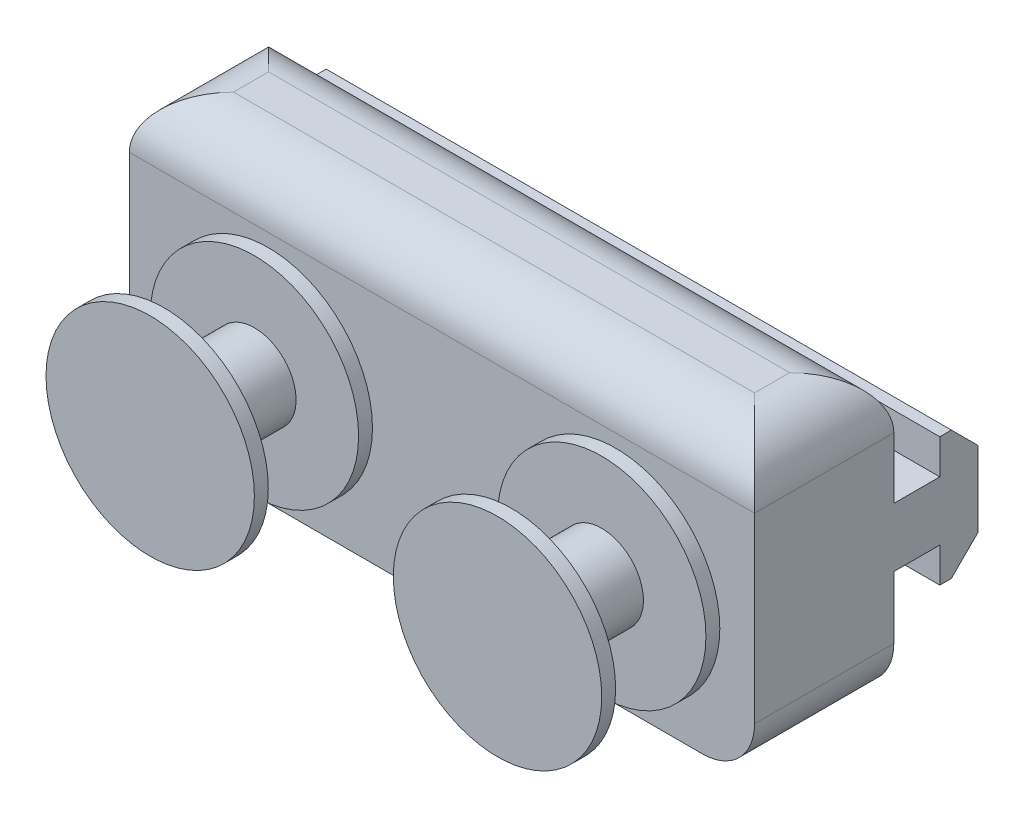
SolidWorks part; units mm, degrees
ref_plane "Front Plane" through (0, 0, 0) normal (0, 0, 1) x (1, 0, 0)
ref_plane "Top Plane" through (0, 0, 0) normal (0, 1, 0) x (1, 0, 0)
ref_plane "Right Plane" through (0, 0, 0) normal (1, 0, 0) x (0, 0, -1)
sketch "Sketch2" plane through (0, 0, 0) normal (1, 0, 0) x (0, 0, -1)
  line L0 (20, -17) -> (20, -5) construction
  line L1 (20, -5) -> (14.5, -5) construction
  line L2 (14.5, -5) -> (14.5, -10) construction
  line L3 (14.5, -10) -> (11.7678, -10) construction
  line L4 (11.7678, -10) -> (7.5, -5.7322) construction
  line L5 (7.5, -5.7322) -> (7.5, -0.5196) construction
  line L6 (7.5, -0.5196) -> (7.2, 0) construction
  line L7 (7.2, 0) -> (7.5, 0.5196) construction
  line L8 (7.5, 0.5196) -> (7.5, 5.7322) construction
  line L9 (7.5, 5.7322) -> (11.7678, 10) construction
  line L10 (11.7678, 10) -> (14.5, 10) construction
  line L11 (14.5, 10) -> (14.5, 5) construction
  line L12 (14.5, 5) -> (20, 5) construction
  line L13 (20, 5) -> (20, 16.9163) construction
  line L14 (17, 19.9163) -> (5, 19.9163) construction
  line L15 (5, 19.9163) -> (5, 14.5) construction
  line L16 (5, 14.5) -> (10, 14.5) construction
  line L17 (10, 14.5) -> (10, 11.7678) construction
  line L18 (10, 11.7678) -> (5.7322, 7.5) construction
  line L19 (5.7322, 7.5) -> (0.5196, 7.5) construction
  line L20 (0.5196, 7.5) -> (0, 7.2) construction
  line L21 (0, 7.2) -> (-0.5196, 7.5) construction
  line L22 (-0.5196, 7.5) -> (-5.7322, 7.5) construction
  line L23 (-5.7322, 7.5) -> (-10, 11.7678) construction
  line L24 (-10, 11.7678) -> (-10, 14.5) construction
  line L25 (-10, 14.5) -> (-5, 14.5) construction
  line L26 (-5, 14.5) -> (-5, 19.9163) construction
  line L27 (-5, 19.9163) -> (-17.0837, 19.9163) construction
  line L28 (-20, 17) -> (-20, 5) construction
  line L29 (-20, 5) -> (-14.5, 5) construction
  line L30 (-14.5, 5) -> (-14.5, 10) construction
  line L31 (-14.5, 10) -> (-11.7678, 10) construction
  line L32 (-11.7678, 10) -> (-7.5, 5.7322) construction
  line L33 (-7.5, 5.7322) -> (-7.5, 0.5196) construction
  line L34 (-7.5, 0.5196) -> (-7.2, 0) construction
  line L35 (-7.2, 0) -> (-7.5, -0.5196) construction
  line L36 (-7.5, -0.5196) -> (-7.5, -5.7322) construction
  line L37 (-7.5, -5.7322) -> (-11.7678, -10) construction
  line L38 (-11.7678, -10) -> (-14.5, -10) construction
  line L39 (-14.5, -10) -> (-14.5, -5) construction
  line L40 (-14.5, -5) -> (-20, -5) construction
  line L41 (-20, -5) -> (-20, -17) construction
  line L42 (-17, -20) -> (17, -20) construction
  line L55 (-21, 3.617) -> (-21, -4.883)
  line L56 (-14.3817, -4.883) -> (-21, -4.883)
  line L57 (-14.3817, -9.883) -> (-14.3817, -4.883)
  line L58 (-12.7101, -9.883) -> (-14.3817, -9.883)
  line L59 (-8.8817, -6.0546) -> (-12.7101, -9.883)
  line L60 (-8.8817, -1.1526) -> (-8.8817, -6.0546)
  line L61 (-8.8817, -0.1134) -> (-8.8817, -1.1526)
  line L62 (-8.8817, 4.7886) -> (-8.8817, -0.1134)
  line L63 (-12.7101, 8.617) -> (-8.8817, 4.7886)
  line L64 (-14.3817, 8.617) -> (-12.7101, 8.617)
  line L65 (-14.3817, 3.617) -> (-14.3817, 8.617)
  line L66 (-21, 3.617) -> (-14.3817, 3.617)
  line L67 (-38.049, -7.3386) -> (-38.049, -11.8386) construction
  line L68 (-37.749, -12.1386) -> (-36.949, -12.1386) construction
  line L69 (-36.949, -12.1386) -> (-36.949, -10.9886) construction
  line L70 (-36.949, -10.9886) -> (-34.349, -10.9886) construction
  line L71 (-34.349, -10.9886) -> (-33.349, -11.9886) construction
  line L72 (-33.349, -11.9886) -> (-33.349, -13.319) construction
  line L73 (-33.349, -13.319) -> (-33.049, -13.8386) construction
  line L74 (-33.049, -13.8386) -> (-33.349, -14.3582) construction
  line L75 (-33.349, -14.3582) -> (-33.349, -15.6886) construction
  line L76 (-33.349, -15.6886) -> (-34.349, -16.6886) construction
  line L77 (-34.349, -16.6886) -> (-36.949, -16.6886) construction
  line L78 (-36.949, -16.6886) -> (-36.949, -15.5386) construction
  line L79 (-36.949, -15.5386) -> (-37.749, -15.5386) construction
  line L80 (-38.049, -15.8386) -> (-38.049, -20.3386) construction
  line L81 (-37.049, -21.3386) -> (-32.549, -21.3386) construction
  line L82 (-32.249, -21.0386) -> (-32.249, -20.2386) construction
  line L83 (-32.249, -20.2386) -> (-33.399, -20.2386) construction
  line L84 (-33.399, -20.2386) -> (-33.399, -17.6386) construction
  line L85 (-33.399, -17.6386) -> (-32.399, -16.6386) construction
  line L86 (-32.399, -16.6386) -> (-31.0686, -16.6386) construction
  line L87 (-31.0686, -16.6386) -> (-30.549, -16.3386) construction
  line L88 (-30.549, -16.3386) -> (-30.0293, -16.6386) construction
  line L89 (-30.0293, -16.6386) -> (-28.699, -16.6386) construction
  line L90 (-28.699, -16.6386) -> (-27.699, -17.6386) construction
  line L91 (-27.699, -17.6386) -> (-27.699, -20.2386) construction
  line L92 (-27.699, -20.2386) -> (-28.849, -20.2386) construction
  line L93 (-28.849, -20.2386) -> (-28.849, -21.0386) construction
  line L94 (-28.549, -21.3386) -> (-24.049, -21.3386) construction
  line L95 (-23.049, -20.3386) -> (-23.049, -15.8386) construction
  line L96 (-23.349, -15.5386) -> (-24.149, -15.5386) construction
  line L97 (-24.149, -15.5386) -> (-24.149, -16.6886) construction
  line L98 (-24.149, -16.6886) -> (-26.749, -16.6886) construction
  line L99 (-26.749, -16.6886) -> (-27.749, -15.6886) construction
  line L100 (-27.749, -15.6886) -> (-27.749, -14.3582) construction
  line L101 (-27.749, -14.3582) -> (-28.049, -13.8386) construction
  line L102 (-28.049, -13.8386) -> (-27.749, -13.319) construction
  line L103 (-27.749, -13.319) -> (-27.749, -11.9886) construction
  line L104 (-27.749, -11.9886) -> (-26.749, -10.9886) construction
  line L105 (-26.749, -10.9886) -> (-24.149, -10.9886) construction
  line L106 (-24.149, -10.9886) -> (-24.149, -12.1386) construction
  line L107 (-24.149, -12.1386) -> (-23.349, -12.1386) construction
  line L108 (-23.049, -11.8386) -> (-23.049, -7.3386) construction
  line L109 (-24.049, -6.3386) -> (-28.549, -6.3386) construction
  line L110 (-28.849, -6.6386) -> (-28.849, -7.4386) construction
  line L111 (-28.849, -7.4386) -> (-27.699, -7.4386) construction
  line L112 (-27.699, -7.4386) -> (-27.699, -10.0386) construction
  line L113 (-27.699, -10.0386) -> (-28.699, -11.0386) construction
  line L114 (-28.699, -11.0386) -> (-30.0293, -11.0386) construction
  line L115 (-30.0293, -11.0386) -> (-30.549, -11.3386) construction
  line L116 (-30.549, -11.3386) -> (-31.0686, -11.0386) construction
  line L117 (-31.0686, -11.0386) -> (-32.399, -11.0386) construction
  line L118 (-32.399, -11.0386) -> (-33.399, -10.0386) construction
  line L119 (-33.399, -10.0386) -> (-33.399, -7.4386) construction
  line L120 (-33.399, -7.4386) -> (-32.249, -7.4386) construction
  line L121 (-32.249, -7.4386) -> (-32.249, -6.6386) construction
  line L122 (-32.549, -6.3386) -> (-37.049, -6.3386) construction
  line L123 (-37.049, -6.3386) -> (-41.049, -6.3386) construction
  line L124 (-24.049, -6.3386) -> (-20.049, -6.3386) construction
  line L125 (-21, 3.617) -> (-21, 19.9163)
  line L126 (-21, 19.9163) -> (-41.049, 19.9163)
  line L127 (-41.049, 19.9163) -> (-41.049, -21.3386)
  line L128 (-41.049, -21.3386) -> (-21, -21.3386)
  line L129 (-21, -21.3386) -> (-21, -5)
  line L130 (-21, -5) -> (-21, 3.617)
  arc A0 (20, 16.9163) -> (17, 19.9163) centre (17, 16.9163) ccw construction
  arc A1 (-17.0837, 19.9163) -> (-20, 17) centre (-17.0837, 17) ccw construction
  arc A2 (-20, -17) -> (-17, -20) centre (-17, -17) ccw construction
  arc A3 (17, -20) -> (20, -17) centre (17, -17) ccw construction
  circle A4 centre (-30.549, -13.8386) radius 1.25 construction
  arc A5 (-38.049, -11.8386) -> (-37.749, -12.1386) centre (-37.749, -11.8386) ccw construction
  arc A6 (-37.749, -15.5386) -> (-38.049, -15.8386) centre (-37.749, -15.8386) ccw construction
  arc A7 (-38.049, -20.3386) -> (-37.049, -21.3386) centre (-37.049, -20.3386) ccw construction
  arc A8 (-32.549, -21.3386) -> (-32.249, -21.0386) centre (-32.549, -21.0386) ccw construction
  arc A9 (-28.849, -21.0386) -> (-28.549, -21.3386) centre (-28.549, -21.0386) ccw construction
  arc A10 (-24.049, -21.3386) -> (-23.049, -20.3386) centre (-24.049, -20.3386) ccw construction
  arc A11 (-23.049, -15.8386) -> (-23.349, -15.5386) centre (-23.349, -15.8386) ccw construction
  arc A12 (-23.349, -12.1386) -> (-23.049, -11.8386) centre (-23.349, -11.8386) ccw construction
  arc A13 (-23.049, -7.3386) -> (-24.049, -6.3386) centre (-24.049, -7.3386) ccw construction
  arc A14 (-28.549, -6.3386) -> (-28.849, -6.6386) centre (-28.549, -6.6386) ccw construction
  arc A15 (-32.249, -6.6386) -> (-32.549, -6.3386) centre (-32.549, -6.6386) ccw construction
  arc A16 (-37.049, -6.3386) -> (-38.049, -7.3386) centre (-37.049, -7.3386) ccw construction
extrude "Boss-Extrude2" add sketch "Sketch2" along normal blind 90 contours L129 L130 L55 L125 L126 L127 L128 | L66 L55 L56 L57 L58 L59 L60 L61 L62 L63 L64 L65 region at (0, -0.633, 14.1602) region at (0, -0.7111, 31.0245)
sketch "Sketch3" plane through (0, -21.3386, 0) normal (0, -1, 0) x (1, 0, 0)
  line L0 (60.0031, 37.5245) -> (60.0031, 33.0245) construction
  line L1 (60.3031, 32.7245) -> (61.1031, 32.7245) construction
  line L2 (61.1031, 32.7245) -> (61.1031, 33.8745) construction
  line L3 (61.1031, 33.8745) -> (63.7031, 33.8745) construction
  line L4 (63.7031, 33.8745) -> (64.7031, 32.8745) construction
  line L5 (64.7031, 32.8745) -> (64.7031, 31.5441) construction
  line L6 (64.7031, 31.5441) -> (65.0031, 31.0245) construction
  line L7 (65.0031, 31.0245) -> (64.7031, 30.5049) construction
  line L8 (64.7031, 30.5049) -> (64.7031, 29.1745) construction
  line L9 (64.7031, 29.1745) -> (63.7031, 28.1745) construction
  line L10 (63.7031, 28.1745) -> (61.1031, 28.1745) construction
  line L11 (61.1031, 28.1745) -> (61.1031, 29.3245) construction
  line L12 (61.1031, 29.3245) -> (60.3031, 29.3245) construction
  line L13 (60.0031, 29.0245) -> (60.0031, 24.5245) construction
  line L14 (61.0031, 23.5245) -> (65.5031, 23.5245) construction
  line L15 (65.8031, 23.8245) -> (65.8031, 24.6245) construction
  line L16 (65.8031, 24.6245) -> (64.6531, 24.6245) construction
  line L17 (64.6531, 24.6245) -> (64.6531, 27.2245) construction
  line L18 (64.6531, 27.2245) -> (65.6531, 28.2245) construction
  line L19 (65.6531, 28.2245) -> (66.9835, 28.2245) construction
  line L20 (66.9835, 28.2245) -> (67.5031, 28.5245) construction
  line L21 (67.5031, 28.5245) -> (68.0228, 28.2245) construction
  line L22 (68.0228, 28.2245) -> (69.3531, 28.2245) construction
  line L23 (69.3531, 28.2245) -> (70.3531, 27.2245) construction
  line L24 (70.3531, 27.2245) -> (70.3531, 24.6245) construction
  line L25 (70.3531, 24.6245) -> (69.2031, 24.6245) construction
  line L26 (69.2031, 24.6245) -> (69.2031, 23.8245) construction
  line L27 (69.5031, 23.5245) -> (74.0031, 23.5245) construction
  line L28 (75.0031, 24.5245) -> (75.0031, 29.0245) construction
  line L29 (74.7031, 29.3245) -> (73.9031, 29.3245) construction
  line L30 (73.9031, 29.3245) -> (73.9031, 28.1745) construction
  line L31 (73.9031, 28.1745) -> (71.3031, 28.1745) construction
  line L32 (71.3031, 28.1745) -> (70.3031, 29.1745) construction
  line L33 (70.3031, 29.1745) -> (70.3031, 30.5049) construction
  line L34 (70.3031, 30.5049) -> (70.0031, 31.0245) construction
  line L35 (70.0031, 31.0245) -> (70.3031, 31.5441) construction
  line L36 (70.3031, 31.5441) -> (70.3031, 32.8745) construction
  line L37 (70.3031, 32.8745) -> (71.3031, 33.8745) construction
  line L38 (71.3031, 33.8745) -> (73.9031, 33.8745) construction
  line L39 (73.9031, 33.8745) -> (73.9031, 32.7245) construction
  line L40 (73.9031, 32.7245) -> (74.7031, 32.7245) construction
  line L41 (75.0031, 33.0245) -> (75.0031, 37.5245) construction
  line L42 (74.0031, 38.5245) -> (69.5031, 38.5245) construction
  line L43 (69.2031, 38.2245) -> (69.2031, 37.4245) construction
  line L44 (69.2031, 37.4245) -> (70.3531, 37.4245) construction
  line L45 (70.3531, 37.4245) -> (70.3531, 34.8245) construction
  line L46 (70.3531, 34.8245) -> (69.3531, 33.8245) construction
  line L47 (69.3531, 33.8245) -> (68.0228, 33.8245) construction
  line L48 (68.0228, 33.8245) -> (67.5031, 33.5245) construction
  line L49 (67.5031, 33.5245) -> (66.9835, 33.8245) construction
  line L50 (66.9835, 33.8245) -> (65.6531, 33.8245) construction
  line L51 (65.6531, 33.8245) -> (64.6531, 34.8245) construction
  line L52 (64.6531, 34.8245) -> (64.6531, 37.4245) construction
  line L53 (64.6531, 37.4245) -> (65.8031, 37.4245) construction
  line L54 (65.8031, 37.4245) -> (65.8031, 38.2245) construction
  line L55 (65.5031, 38.5245) -> (61.0031, 38.5245) construction
  line L56 (90, 31.0245) -> (75, 31.0245) construction
  line L59 (90, 41.049) -> (90, 21) construction
  line L60 (0, 31.0245) -> (15, 31.0245) construction
  line L61 (0, 41.049) -> (0, 21) construction
  line L62 (0, 31.0245) -> (90, 31.0245) construction
  line L117 (45, 31.0245) -> (60, 31.0245) construction
  line L118 (59.5031, 37.5245) -> (59.5031, 33.0245)
  line L119 (90, 21) -> (0, 21) construction
  line L120 (60, 21) -> (60, 41.049) construction
  line L121 (90, 41.049) -> (0, 41.049) construction
  line L122 (45, 41.049) -> (45, 21) construction
  line L123 (24.4969, 38.5245) -> (28.9969, 38.5245) construction
  line L124 (24.1969, 37.4245) -> (24.1969, 38.2245) construction
  line L125 (25.3469, 37.4245) -> (24.1969, 37.4245) construction
  line L126 (25.3469, 34.8245) -> (25.3469, 37.4245) construction
  line L127 (24.3469, 33.8245) -> (25.3469, 34.8245) construction
  line L128 (23.0165, 33.8245) -> (24.3469, 33.8245) construction
  line L129 (22.4969, 33.5245) -> (23.0165, 33.8245) construction
  line L130 (21.9772, 33.8245) -> (22.4969, 33.5245) construction
  line L131 (20.6469, 33.8245) -> (21.9772, 33.8245) construction
  line L132 (19.6469, 34.8245) -> (20.6469, 33.8245) construction
  line L133 (19.6469, 37.4245) -> (19.6469, 34.8245) construction
  line L134 (20.7969, 37.4245) -> (19.6469, 37.4245) construction
  line L135 (20.7969, 38.2245) -> (20.7969, 37.4245) construction
  line L136 (15.9969, 38.5245) -> (20.4969, 38.5245) construction
  line L137 (14.9969, 33.0245) -> (14.9969, 37.5245) construction
  line L138 (16.0969, 32.7245) -> (15.2969, 32.7245) construction
  line L139 (16.0969, 33.8745) -> (16.0969, 32.7245) construction
  line L140 (18.6969, 33.8745) -> (16.0969, 33.8745) construction
  line L141 (19.6969, 32.8745) -> (18.6969, 33.8745) construction
  line L142 (19.6969, 31.5441) -> (19.6969, 32.8745) construction
  line L143 (19.9969, 31.0245) -> (19.6969, 31.5441) construction
  line L144 (19.6969, 30.5049) -> (19.9969, 31.0245) construction
  line L145 (19.6969, 29.1745) -> (19.6969, 30.5049) construction
  line L146 (18.6969, 28.1745) -> (19.6969, 29.1745) construction
  line L147 (16.0969, 28.1745) -> (18.6969, 28.1745) construction
  line L148 (16.0969, 29.3245) -> (16.0969, 28.1745) construction
  line L149 (15.2969, 29.3245) -> (16.0969, 29.3245) construction
  line L150 (14.9969, 24.5245) -> (14.9969, 29.0245) construction
  line L151 (20.4969, 23.5245) -> (15.9969, 23.5245) construction
  line L152 (20.7969, 24.6245) -> (20.7969, 23.8245) construction
  line L153 (19.6469, 24.6245) -> (20.7969, 24.6245) construction
  line L154 (19.6469, 27.2245) -> (19.6469, 24.6245) construction
  line L155 (20.6469, 28.2245) -> (19.6469, 27.2245) construction
  line L156 (21.9772, 28.2245) -> (20.6469, 28.2245) construction
  line L157 (22.4969, 28.5245) -> (21.9772, 28.2245) construction
  line L158 (23.0165, 28.2245) -> (22.4969, 28.5245) construction
  line L159 (24.3469, 28.2245) -> (23.0165, 28.2245) construction
  line L160 (25.3469, 27.2245) -> (24.3469, 28.2245) construction
  line L161 (25.3469, 24.6245) -> (25.3469, 27.2245) construction
  line L162 (24.1969, 24.6245) -> (25.3469, 24.6245) construction
  line L163 (24.1969, 23.8245) -> (24.1969, 24.6245) construction
  line L164 (28.9969, 23.5245) -> (24.4969, 23.5245) construction
  line L165 (29.9969, 29.0245) -> (29.9969, 24.5245) construction
  line L166 (28.8969, 29.3245) -> (29.6969, 29.3245) construction
  line L167 (28.8969, 28.1745) -> (28.8969, 29.3245) construction
  line L168 (26.2969, 28.1745) -> (28.8969, 28.1745) construction
  line L169 (25.2969, 29.1745) -> (26.2969, 28.1745) construction
  line L170 (25.2969, 30.5049) -> (25.2969, 29.1745) construction
  line L171 (24.9969, 31.0245) -> (25.2969, 30.5049) construction
  line L172 (25.2969, 31.5441) -> (24.9969, 31.0245) construction
  line L173 (25.2969, 32.8745) -> (25.2969, 31.5441) construction
  line L174 (26.2969, 33.8745) -> (25.2969, 32.8745) construction
  line L175 (28.8969, 33.8745) -> (26.2969, 33.8745) construction
  line L176 (28.8969, 32.7245) -> (28.8969, 33.8745) construction
  line L177 (29.6969, 32.7245) -> (28.8969, 32.7245) construction
  line L178 (29.9969, 37.5245) -> (29.9969, 33.0245) construction
  line L179 (60.3031, 32.2245) -> (61.6031, 32.2245)
  line L180 (61.6031, 32.2245) -> (61.6031, 33.3745)
  line L181 (61.6031, 33.3745) -> (63.496, 33.3745)
  line L182 (63.496, 33.3745) -> (64.2031, 32.6674)
  line L183 (64.2031, 32.6674) -> (64.2031, 31.4101)
  line L184 (64.2031, 31.4101) -> (64.4258, 31.0245)
  line L185 (64.4258, 31.0245) -> (64.2031, 30.6388)
  line L186 (64.2031, 30.6388) -> (64.2031, 29.3816)
  line L187 (64.2031, 29.3816) -> (63.496, 28.6745)
  line L188 (63.496, 28.6745) -> (61.6031, 28.6745)
  line L189 (61.6031, 28.6745) -> (61.6031, 29.8245)
  line L190 (61.6031, 29.8245) -> (60.3031, 29.8245)
  line L191 (59.5031, 29.0245) -> (59.5031, 24.5245)
  line L192 (61.0031, 23.0245) -> (65.5031, 23.0245)
  line L193 (66.3031, 23.8245) -> (66.3031, 25.1245)
  line L194 (66.3031, 25.1245) -> (65.1531, 25.1245)
  line L195 (65.1531, 25.1245) -> (65.1531, 27.0174)
  line L196 (65.1531, 27.0174) -> (65.8602, 27.7245)
  line L197 (65.8602, 27.7245) -> (67.1175, 27.7245)
  line L198 (67.1175, 27.7245) -> (67.5031, 27.9471)
  line L199 (67.5031, 27.9471) -> (67.8888, 27.7245)
  line L200 (67.8888, 27.7245) -> (69.146, 27.7245)
  line L201 (69.146, 27.7245) -> (69.8531, 27.0174)
  line L202 (69.8531, 27.0174) -> (69.8531, 25.1245)
  line L203 (69.8531, 25.1245) -> (68.7031, 25.1245)
  line L204 (68.7031, 25.1245) -> (68.7031, 23.8245)
  line L205 (69.5031, 23.0245) -> (74.0031, 23.0245)
  line L206 (75.5031, 24.5245) -> (75.5031, 29.0245)
  line L207 (74.7031, 29.8245) -> (73.4031, 29.8245)
  line L208 (73.4031, 29.8245) -> (73.4031, 28.6745)
  line L209 (73.4031, 28.6745) -> (71.5102, 28.6745)
  line L210 (71.5102, 28.6745) -> (70.8031, 29.3816)
  line L211 (70.8031, 29.3816) -> (70.8031, 30.6388)
  line L212 (70.8031, 30.6388) -> (70.5805, 31.0245)
  line L213 (70.5805, 31.0245) -> (70.8031, 31.4101)
  line L214 (70.8031, 31.4101) -> (70.8031, 32.6674)
  line L215 (70.8031, 32.6674) -> (71.5102, 33.3745)
  line L216 (71.5102, 33.3745) -> (73.4031, 33.3745)
  line L217 (73.4031, 33.3745) -> (73.4031, 32.2245)
  line L218 (73.4031, 32.2245) -> (74.7031, 32.2245)
  line L219 (75.5031, 33.0245) -> (75.5031, 37.5245)
  line L220 (74.0031, 39.0245) -> (69.5031, 39.0245)
  line L221 (68.7031, 38.2245) -> (68.7031, 36.9245)
  line L222 (68.7031, 36.9245) -> (69.8531, 36.9245)
  line L223 (69.8531, 36.9245) -> (69.8531, 35.0316)
  line L224 (69.8531, 35.0316) -> (69.146, 34.3245)
  line L225 (69.146, 34.3245) -> (67.8888, 34.3245)
  line L226 (67.8888, 34.3245) -> (67.5031, 34.1018)
  line L227 (67.5031, 34.1018) -> (67.1175, 34.3245)
  line L228 (67.1175, 34.3245) -> (65.8602, 34.3245)
  line L229 (65.8602, 34.3245) -> (65.1531, 35.0316)
  line L230 (65.1531, 35.0316) -> (65.1531, 36.9245)
  line L231 (65.1531, 36.9245) -> (66.3031, 36.9245)
  line L232 (66.3031, 36.9245) -> (66.3031, 38.2245)
  line L233 (65.5031, 39.0245) -> (61.0031, 39.0245)
  line L234 (30.4969, 37.5245) -> (30.4969, 33.0245)
  line L235 (29.6969, 32.2245) -> (28.3969, 32.2245)
  line L236 (28.3969, 32.2245) -> (28.3969, 33.3745)
  line L237 (28.3969, 33.3745) -> (26.504, 33.3745)
  line L238 (26.504, 33.3745) -> (25.7969, 32.6674)
  line L239 (25.7969, 32.6674) -> (25.7969, 31.4101)
  line L240 (25.7969, 31.4101) -> (25.5742, 31.0245)
  line L241 (25.5742, 31.0245) -> (25.7969, 30.6388)
  line L242 (25.7969, 30.6388) -> (25.7969, 29.3816)
  line L243 (25.7969, 29.3816) -> (26.504, 28.6745)
  line L244 (26.504, 28.6745) -> (28.3969, 28.6745)
  line L245 (28.3969, 28.6745) -> (28.3969, 29.8245)
  line L246 (28.3969, 29.8245) -> (29.6969, 29.8245)
  line L247 (30.4969, 29.0245) -> (30.4969, 24.5245)
  line L248 (28.9969, 23.0245) -> (24.4969, 23.0245)
  line L249 (23.6969, 23.8245) -> (23.6969, 25.1245)
  line L250 (23.6969, 25.1245) -> (24.8469, 25.1245)
  line L251 (24.8469, 25.1245) -> (24.8469, 27.0174)
  line L252 (24.8469, 27.0174) -> (24.1398, 27.7245)
  line L253 (24.1398, 27.7245) -> (22.8825, 27.7245)
  line L254 (22.8825, 27.7245) -> (22.4969, 27.9471)
  line L255 (22.4969, 27.9471) -> (22.1112, 27.7245)
  line L256 (22.1112, 27.7245) -> (20.854, 27.7245)
  line L257 (20.854, 27.7245) -> (20.1469, 27.0174)
  line L258 (20.1469, 27.0174) -> (20.1469, 25.1245)
  line L259 (20.1469, 25.1245) -> (21.2969, 25.1245)
  line L260 (21.2969, 25.1245) -> (21.2969, 23.8245)
  line L261 (20.4969, 23.0245) -> (15.9969, 23.0245)
  line L262 (14.4969, 24.5245) -> (14.4969, 29.0245)
  line L263 (15.2969, 29.8245) -> (16.5969, 29.8245)
  line L264 (16.5969, 29.8245) -> (16.5969, 28.6745)
  line L265 (16.5969, 28.6745) -> (18.4898, 28.6745)
  line L266 (18.4898, 28.6745) -> (19.1969, 29.3816)
  line L267 (19.1969, 29.3816) -> (19.1969, 30.6388)
  line L268 (19.1969, 30.6388) -> (19.4195, 31.0245)
  line L269 (19.4195, 31.0245) -> (19.1969, 31.4101)
  line L270 (19.1969, 31.4101) -> (19.1969, 32.6674)
  line L271 (19.1969, 32.6674) -> (18.4898, 33.3745)
  line L272 (18.4898, 33.3745) -> (16.5969, 33.3745)
  line L273 (16.5969, 33.3745) -> (16.5969, 32.2245)
  line L274 (16.5969, 32.2245) -> (15.2969, 32.2245)
  line L275 (14.4969, 33.0245) -> (14.4969, 37.5245)
  line L276 (15.9969, 39.0245) -> (20.4969, 39.0245)
  line L277 (21.2969, 38.2245) -> (21.2969, 36.9245)
  line L278 (21.2969, 36.9245) -> (20.1469, 36.9245)
  line L279 (20.1469, 36.9245) -> (20.1469, 35.0316)
  line L280 (20.1469, 35.0316) -> (20.854, 34.3245)
  line L281 (20.854, 34.3245) -> (22.1112, 34.3245)
  line L282 (22.1112, 34.3245) -> (22.4969, 34.1018)
  line L283 (22.4969, 34.1018) -> (22.8825, 34.3245)
  line L284 (22.8825, 34.3245) -> (24.1398, 34.3245)
  line L285 (24.1398, 34.3245) -> (24.8469, 35.0316)
  line L286 (24.8469, 35.0316) -> (24.8469, 36.9245)
  line L287 (24.8469, 36.9245) -> (23.6969, 36.9245)
  line L288 (23.6969, 36.9245) -> (23.6969, 38.2245)
  line L289 (24.4969, 39.0245) -> (28.9969, 39.0245)
  arc A1 (60.0031, 33.0245) -> (60.3031, 32.7245) centre (60.3031, 33.0245) ccw construction
  arc A2 (60.3031, 29.3245) -> (60.0031, 29.0245) centre (60.3031, 29.0245) ccw construction
  arc A3 (60.0031, 24.5245) -> (61.0031, 23.5245) centre (61.0031, 24.5245) ccw construction
  arc A4 (65.5031, 23.5245) -> (65.8031, 23.8245) centre (65.5031, 23.8245) ccw construction
  arc A5 (69.2031, 23.8245) -> (69.5031, 23.5245) centre (69.5031, 23.8245) ccw construction
  arc A6 (74.0031, 23.5245) -> (75.0031, 24.5245) centre (74.0031, 24.5245) ccw construction
  arc A7 (75.0031, 29.0245) -> (74.7031, 29.3245) centre (74.7031, 29.0245) ccw construction
  arc A8 (74.7031, 32.7245) -> (75.0031, 33.0245) centre (74.7031, 33.0245) ccw construction
  arc A9 (75.0031, 37.5245) -> (74.0031, 38.5245) centre (74.0031, 37.5245) ccw construction
  arc A10 (69.5031, 38.5245) -> (69.2031, 38.2245) centre (69.5031, 38.2245) ccw construction
  arc A11 (65.8031, 38.2245) -> (65.5031, 38.5245) centre (65.5031, 38.2245) ccw construction
  arc A12 (61.0031, 38.5245) -> (60.0031, 37.5245) centre (61.0031, 37.5245) ccw construction
  arc A25 (28.9969, 38.5245) -> (29.9969, 37.5245) centre (28.9969, 37.5245) cw construction
  arc A26 (24.1969, 38.2245) -> (24.4969, 38.5245) centre (24.4969, 38.2245) cw construction
  arc A27 (20.4969, 38.5245) -> (20.7969, 38.2245) centre (20.4969, 38.2245) cw construction
  arc A28 (14.9969, 37.5245) -> (15.9969, 38.5245) centre (15.9969, 37.5245) cw construction
  arc A29 (15.2969, 32.7245) -> (14.9969, 33.0245) centre (15.2969, 33.0245) cw construction
  arc A30 (14.9969, 29.0245) -> (15.2969, 29.3245) centre (15.2969, 29.0245) cw construction
  arc A31 (15.9969, 23.5245) -> (14.9969, 24.5245) centre (15.9969, 24.5245) cw construction
  arc A32 (20.7969, 23.8245) -> (20.4969, 23.5245) centre (20.4969, 23.8245) cw construction
  arc A33 (24.4969, 23.5245) -> (24.1969, 23.8245) centre (24.4969, 23.8245) cw construction
  arc A34 (29.9969, 24.5245) -> (28.9969, 23.5245) centre (28.9969, 24.5245) cw construction
  arc A35 (29.6969, 29.3245) -> (29.9969, 29.0245) centre (29.6969, 29.0245) cw construction
  arc A36 (29.9969, 33.0245) -> (29.6969, 32.7245) centre (29.6969, 33.0245) cw construction
  arc A37 (59.5031, 33.0245) -> (60.3031, 32.2245) centre (60.3031, 33.0245) ccw
  arc A38 (60.3031, 29.8245) -> (59.5031, 29.0245) centre (60.3031, 29.0245) ccw
  arc A39 (59.5031, 24.5245) -> (61.0031, 23.0245) centre (61.0031, 24.5245) ccw
  arc A40 (65.5031, 23.0245) -> (66.3031, 23.8245) centre (65.5031, 23.8245) ccw
  arc A41 (68.7031, 23.8245) -> (69.5031, 23.0245) centre (69.5031, 23.8245) ccw
  arc A42 (74.0031, 23.0245) -> (75.5031, 24.5245) centre (74.0031, 24.5245) ccw
  arc A43 (75.5031, 29.0245) -> (74.7031, 29.8245) centre (74.7031, 29.0245) ccw
  arc A44 (74.7031, 32.2245) -> (75.5031, 33.0245) centre (74.7031, 33.0245) ccw
  arc A45 (75.5031, 37.5245) -> (74.0031, 39.0245) centre (74.0031, 37.5245) ccw
  arc A46 (69.5031, 39.0245) -> (68.7031, 38.2245) centre (69.5031, 38.2245) ccw
  arc A47 (66.3031, 38.2245) -> (65.5031, 39.0245) centre (65.5031, 38.2245) ccw
  arc A48 (61.0031, 39.0245) -> (59.5031, 37.5245) centre (61.0031, 37.5245) ccw
  arc A49 (28.9969, 39.0245) -> (30.4969, 37.5245) centre (28.9969, 37.5245) cw
  arc A50 (30.4969, 33.0245) -> (29.6969, 32.2245) centre (29.6969, 33.0245) cw
  arc A51 (29.6969, 29.8245) -> (30.4969, 29.0245) centre (29.6969, 29.0245) cw
  arc A52 (30.4969, 24.5245) -> (28.9969, 23.0245) centre (28.9969, 24.5245) cw
  arc A53 (24.4969, 23.0245) -> (23.6969, 23.8245) centre (24.4969, 23.8245) cw
  arc A54 (21.2969, 23.8245) -> (20.4969, 23.0245) centre (20.4969, 23.8245) cw
  arc A55 (15.9969, 23.0245) -> (14.4969, 24.5245) centre (15.9969, 24.5245) cw
  arc A56 (14.4969, 29.0245) -> (15.2969, 29.8245) centre (15.2969, 29.0245) cw
  arc A57 (15.2969, 32.2245) -> (14.4969, 33.0245) centre (15.2969, 33.0245) cw
  arc A58 (14.4969, 37.5245) -> (15.9969, 39.0245) centre (15.9969, 37.5245) cw
  arc A59 (20.4969, 39.0245) -> (21.2969, 38.2245) centre (20.4969, 38.2245) cw
  arc A60 (23.6969, 38.2245) -> (24.4969, 39.0245) centre (24.4969, 38.2245) cw
  point P83 (90, 31.0245)
  dimension "D1" = 0.5
extrude "Cut-Extrude1" cut sketch "Sketch3" against normal blind 30 contours L233 A48 L118 A37 L179 L180 L181 L182 L183 L184 L185 L186 L187 L188 L189 L190 A38 L191 A39 L192 A40 L193 L194 L195 L196 L197 L198 L199 L200 L201 L202 L203 L204 A41 L205 A42 L206 A43 L207 L208 L209 L210 L211 L212 L213 L214 L215 L216 L217 L218 A44 | A49 L234 A50 L235 L236 L237 L238 L239 L240 L241 L242 L243 L244 L245 L246 A51 L247 A52 L248 A53 L249 L250 L251 L252 L253 L254 L255 L256 L257 L258 L259 L260 A54 L261 A55 L262 A56 L263 L264 L265 L266 L267 L268 L269 L270 L271 L272 L273 L274 A57 L275 A58 L276 A59 L277 L278 L279 L280 L281 L282 L283 L284 L285 L286 L287 L288 A60 L289 region at (67.5031, -21.3386, 31.0245)
fillet "Fillet1" radius 7.5 6 edges at (0, -21.3386, 31.0245) (90, -21.3386, 31.0245) (90, 19.9163, 31.0245) (45, 19.9163, 41.049) (0, 19.9163, 31.0245) (45, 19.9163, 21)
sketch "Sketch4" plane through (0, 0, 41.049) normal (0, 0, 1) x (1, 0, 0)
  line L0 (45, 12.4163) -> (45, -21.3386) construction
  line L1 (90, 12.4163) -> (0, 12.4163) construction
  line L2 (82.5, -21.3386) -> (7.5, -21.3386) construction
  line L3 (45, -4.4611) -> (20, -4.4611) construction
  circle A0 centre (20, -4.4611) radius 15
  circle A1 centre (70, -4.4611) radius 15
extrude "Boss-Extrude4" add sketch "Sketch4" along normal blind 2 contours A1 | A0
sketch "Sketch5" plane through (0, 0, 43.049) normal (0, 0, 1) x (1, 0, 0)
  circle A0 centre (20, -4.4611) radius 6
  circle A1 centre (70, -4.4611) radius 6
  point P6 (0, 0)
extrude "Boss-Extrude5" add sketch "Sketch5" along normal blind 13 contours A0 | A1
sketch "Sketch7" plane through (0, 0, 56.049) normal (0, 0, 1) x (1, 0, 0)
  circle A0 centre (20, -4.4611) radius 15
  circle A1 centre (70, -4.4611) radius 15
extrude "Boss-Extrude6" add sketch "Sketch7" along normal blind 2 contours A1 | A0
